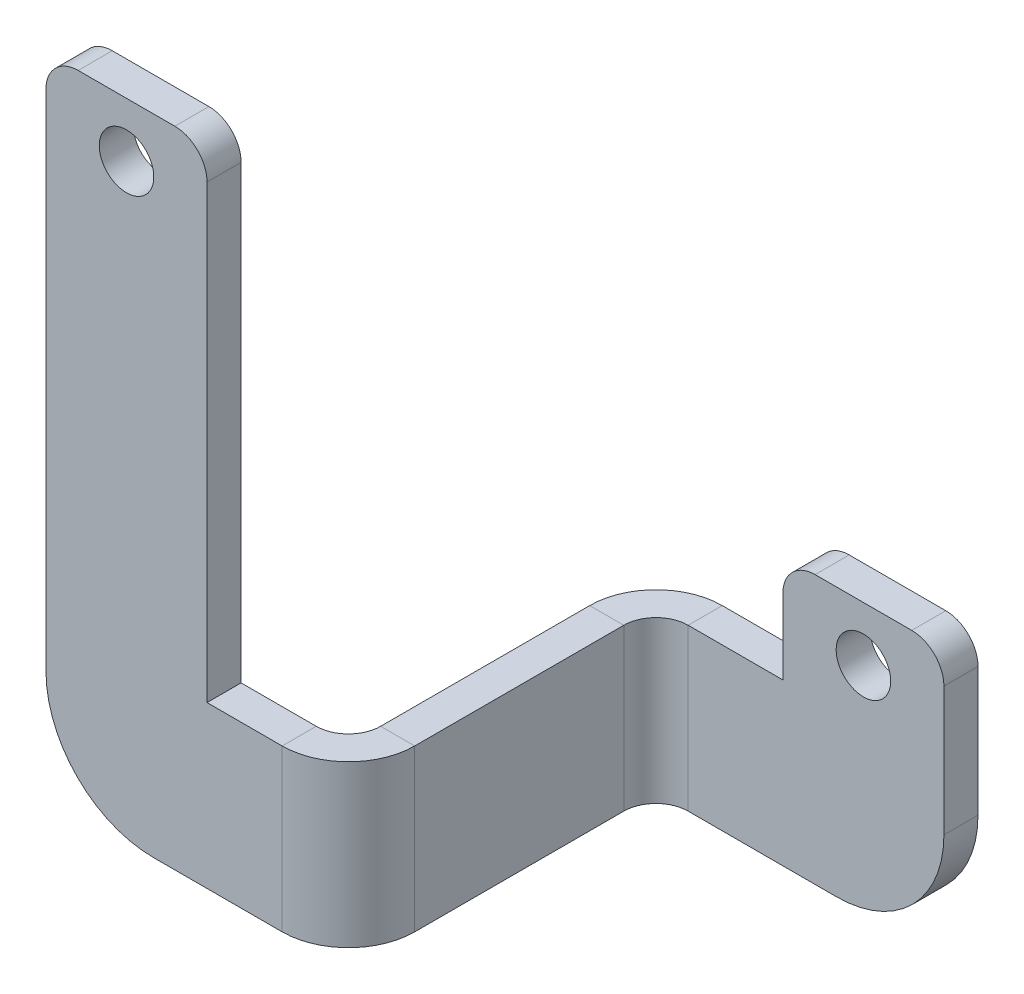
SolidWorks part; units mm, degrees
note: The reader was unsure of these and kept them because the rebuilt part matched: flange length of "Edge-Flange1", "Edge-Flange2".
material "Custom Plastic"
ref_plane "X-Y Datum" through (0, 0, 0) normal (0, 0, 1) x (1, 0, 0)
ref_plane "X-Z Datum" through (0, 0, 0) normal (0, 1, 0) x (1, 0, 0)
ref_plane "Y-Z Datum" through (0, 0, 0) normal (1, 0, 0) x (0, 0, -1)
sketch "Sketch1" plane through (0, 0, 0) normal (0, 0, 1) x (1, 0, 0)
  line L1 (-12.5, -7.5) -> (12.5, -7.5)
  line L2 (-12.5, -7.5) -> (-12.5, 7.5)
  line L3 (-12.5, 7.5) -> (12.5, 7.5)
  line L4 (12.5, -7.5) -> (12.5, 7.5)
  line L5 (-12.5, -7.5) -> (12.5, 7.5) construction
  line L6 (-12.5, 7.5) -> (12.5, -7.5) construction
  point P0 (0, 0)
  dimension "D1" = 25
  dimension "D2" = 15
base flange "Base-Flange1" sketch "Sketch1" thickness 3.175 reverse thickness direction no parameters "D1"=10
edge flange "Edge-Flange1" sketch "Sketch8" flange angle 90 flange length 28.65 flange position material outside bend radius 3 thickness 3.175 parameters "D6"=10
sketch "Sketch8" plane through (12.5, 0, -3.175) normal (-1, 0, 0) x (0, 1, 0)
  line L2 (-7.5, 0) -> (-7.5, 25.475)
  line L3 (-7.5, 25.475) -> (7.5, 25.475)
  line L4 (7.5, 25.475) -> (7.5, 0)
  line L5 (7.5, 0) -> (-7.5, 0) construction
  line L6 (7.5, 0) -> (-7.5, 0)
bend "EdgeBend1" bend radius 3 bend angle 90 parameters "D5"=1
edge flange "Edge-Flange2" sketch "Sketch11" flange angle 90 flange length 30 flange position material outside bend radius 3 thickness 3.175 parameters "D6"=10
sketch "Sketch11" plane through (15.675, 0, -28.65) normal (0, 0, 1) x (0, -1, 0)
  line L2 (-7.5, 0) -> (-7.5, 26.825)
  line L3 (-7.5, 26.825) -> (7.5, 26.825)
  line L4 (7.5, 26.825) -> (7.5, 0)
  line L5 (7.5, 0) -> (-7.5, 0) construction
  line L6 (7.5, 0) -> (-7.5, 0)
bend "EdgeBend2" bend radius 3 bend angle 90 parameters "D5"=2
sketch "Sketch12" plane through (0, 7.5, 0) normal (0, 1, 0) x (1, 0, 0)
  line L0 (9.5, 0) -> (-12.5, 0) construction
  line L1 (-12.5, 3.175) -> (2.5, 3.175)
  line L2 (-12.5, 3.175) -> (-12.5, 0)
  line L3 (-12.5, 0) -> (2.5, 0)
  line L4 (2.5, 3.175) -> (2.5, 0)
  dimension "D1" = 15
extrude "Boss-Extrude1" add sketch "Sketch12" along normal blind 45
sketch "Sketch15" plane through (0, 0, -3.175) normal (0, 0, -1) x (-1, 0, 0)
  line L0 (5, 52.5) -> (5, 47.42)
  line L3 (-2.5, 52.5) -> (12.5, 52.5) construction
  circle A2 centre (5, 47.42) radius 2.54
  dimension "D1" = 5.08
extrude "Cut-Extrude2" cut sketch "Sketch15" against normal through all
sketch "Sketch19" plane through (0, 7.5, 0) normal (0, 1, 0) x (1, 0, 0)
  line L0 (42.5, 28.65) -> (18.675, 28.65) construction
  line L1 (42.5, 31.825) -> (27.5, 31.825)
  line L2 (42.5, 31.825) -> (42.5, 28.65)
  line L3 (42.5, 28.65) -> (27.5, 28.65)
  line L4 (27.5, 31.825) -> (27.5, 28.65)
  dimension "D1" = 15
extrude "Boss-Extrude2" add sketch "Sketch19" along normal blind 10
sketch "Sketch21" plane through (0, 0, -31.825) normal (0, 0, -1) x (-1, 0, 0)
  line L0 (-35, 17.5) -> (-35, 12.42)
  line L2 (-42.5, 17.5) -> (-27.5, 17.5) construction
  circle A1 centre (-35, 12.42) radius 2.54
extrude "Cut-Extrude3" cut sketch "Sketch21" against normal through all
fillet "Fillet2" radius 3 4 edges at (27.5, 17.5, -30.2375) (42.5, 17.5, -30.2375) (2.5, 52.5, -1.5875) (-12.5, 52.5, -1.5875)
fillet "Fillet3" radius 10 2 edges at (42.5, -7.5, -30.2375) (-12.5, -7.5, -1.5875)
sketch "Bend-Lines1" [suppressed] plane through (0, 0, 0) normal (0, 1, 0) x (1, 0, 0)
sketch "Bounding-Box1" [suppressed] plane through (0, 0, 0) normal (0, 1, 0) x (1, 0, 0)
sheet metal parameters "Sheet-Metal1" thickness 3.175 parameters "D1"=10
flat pattern "Flat-Pattern1" [suppressed]
sketch "Bend-Lines2" plane through (0, 0, 0) normal (0, 1, 0) x (1, 0, 0)
sketch3d "Bounding-Box2" [suppressed]
  line L0 (15, -7.5, 0) -> (-15, -7.5, 0) construction
  line L1 (15, 7.5, 0) -> (-15, 7.5, 0) construction
  line L2 (15, -7.5, 0) -> (15, 7.5, 0) construction
  line L3 (-15, -7.5, 0) -> (-15, 7.5, 0) construction
sheet metal parameters "Sheet-Metal2" thickness 3.175 parameters "D1"=10
flat pattern "Flat-Pattern1"
sketch "Bend-Lines2" plane through (0, 0, 0) normal (0, 0, 1) x (1, 0, 0)
  line L0 (15.603, -7.5) -> (15.603, 7.5) construction
  line L1 (15.603, -7.5) -> (15.603, 7.5) construction
sketch3d "Bounding-Box2" [suppressed]
  line L0 (-15, -7.5, 0) -> (38.031, -7.5, 0) construction
  line L1 (-15, 7.5, 0) -> (38.031, 7.5, 0) construction
  line L2 (-15, -7.5, 0) -> (-15, 7.5, 0) construction
  line L3 (38.031, -7.5, 0) -> (38.031, 7.5, 0) construction
bend of the flat pattern "Flatten-<EdgeBend1>1"
sheet metal parameters "Sheet-Metal3" thickness 3.175 parameters "D1"=10
flat pattern "Flat-Pattern1"
sketch "Bend-Lines2" plane through (0, 0, 0) normal (0, 0, 1) x (1, 0, 0)
  line L0 (23.103, -7.5) -> (23.103, 7.5) construction
  line L1 (23.103, -7.5) -> (23.103, 7.5) construction
  line L2 (46.134, -7.5) -> (46.134, 7.5) construction
  line L3 (46.134, -7.5) -> (46.134, 7.5) construction
sketch3d "Bounding-Box2" [suppressed]
  line L0 (-22.5, -7.5, 0) -> (73.5621, -7.5, 0) construction
  line L1 (-22.5, 7.5, 0) -> (73.5621, 7.5, 0) construction
  line L2 (-22.5, -7.5, 0) -> (-22.5, 7.5, 0) construction
  line L3 (73.5621, -7.5, 0) -> (73.5621, 7.5, 0) construction
bend of the flat pattern "Flatten-<EdgeBend1>1"
bend of the flat pattern "Flatten-<EdgeBend2>1"
sheet metal parameters "Sheet-Metal4" thickness 3.175 parameters "D1"=10
flat pattern "Flat-Pattern1"
sketch "Bend-Lines2" plane through (0, 0, 0) normal (0, 0, 1) x (1, 0, 0)
  line L0 (20.603, -7.5) -> (20.603, 7.5) construction
  line L1 (20.603, -7.5) -> (20.603, 7.5) construction
  line L2 (53.634, -7.5) -> (53.634, 7.5) construction
  line L3 (53.634, -7.5) -> (53.634, 7.5) construction
sketch3d "Bounding-Box2" [suppressed]
  line L0 (-20, -7.5, 0) -> (81.0621, -7.5, 0) construction
  line L1 (-20, 41.5, 0) -> (81.0621, 41.5, 0) construction
  line L2 (-20, -7.5, 0) -> (-20, 41.5, 0) construction
  line L3 (81.0621, -7.5, 0) -> (81.0621, 41.5, 0) construction
bend of the flat pattern "Flatten-<EdgeBend1>1"
bend of the flat pattern "Flatten-<EdgeBend2>1"
sheet metal parameters "Sheet-Metal6" thickness 3.175 parameters "D1"=10
flat pattern "Flat-Pattern1" [suppressed]
sketch "Bend-Lines2" plane through (0, 0, 0) normal (0, 0, 1) x (1, 0, 0)
  line L0 (25.603, -10) -> (25.603, 10) construction
  line L1 (25.603, -10) -> (25.603, 10) construction
  line L2 (51.634, -10) -> (51.634, 10) construction
  line L3 (51.634, -10) -> (51.634, 10) construction
sketch3d "Bounding-Box2" [suppressed]
  line L0 (-25, -10, 0) -> (74.0621, -10, 0) construction
  line L1 (-25, 32, 0) -> (74.0621, 32, 0) construction
  line L2 (-25, -10, 0) -> (-25, 32, 0) construction
  line L3 (74.0621, -10, 0) -> (74.0621, 32, 0) construction
bend of the flat pattern "Flatten-<EdgeBend1>1"
bend of the flat pattern "Flatten-<EdgeBend2>1"
sketch "Sketch14-1" [suppressed] plane through (24.0621, 0, -3.175) normal (0, 0, -1) x (-1, 0, 0)
  line L0 (-50, 0) -> (-44.92, 0)
  circle A0 centre (-44.92, 0) radius 2.54
  dimension "D1" = 5.08
sheet metal parameters "Sheet-Metal7" thickness 3.175 parameters "D1"=10
flat pattern "Flat-Pattern1"
sketch "Bend-Lines2" plane through (0, 0, 0) normal (0, 0, 1) x (1, 0, 0)
  line L0 (23.103, -7.5) -> (23.103, 7.5) construction
  line L1 (23.103, -7.5) -> (23.103, 7.5) construction
  line L2 (49.134, -7.5) -> (49.134, 7.5) construction
  line L3 (49.134, -7.5) -> (49.134, 7.5) construction
sketch3d "Bounding-Box2" [suppressed]
  line L0 (-22.5, -7.5, 0) -> (76.5621, -7.5, 0) construction
  line L1 (-22.5, 31.5, 0) -> (76.5621, 31.5, 0) construction
  line L2 (-22.5, -7.5, 0) -> (-22.5, 31.5, 0) construction
  line L3 (76.5621, -7.5, 0) -> (76.5621, 31.5, 0) construction
bend of the flat pattern "Flatten-<EdgeBend1>1"
bend of the flat pattern "Flatten-<EdgeBend2>1"
sheet metal parameters "Sheet-Metal8" thickness 3.175 parameters "D1"=10
flat pattern "Flat-Pattern1"
sketch "Bend-Lines2" plane through (0, 0, 0) normal (0, 0, 1) x (1, 0, 0)
  line L0 (13.103, -7.5) -> (13.103, 7.5) construction
  line L1 (13.103, -7.5) -> (13.103, 7.5) construction
  line L2 (39.784, -7.5) -> (39.784, 7.5) construction
  line L3 (39.784, -7.5) -> (39.784, 7.5) construction
sketch3d "Bounding-Box2" [suppressed]
  line L0 (-12.5, -7.5, 0) -> (67.2121, -7.5, 0) construction
  line L1 (-12.5, 52.5, 0) -> (67.2121, 52.5, 0) construction
  line L2 (-12.5, -7.5, 0) -> (-12.5, 52.5, 0) construction
  line L3 (67.2121, -7.5, 0) -> (67.2121, 52.5, 0) construction
bend of the flat pattern "Flatten-<EdgeBend1>1"
bend of the flat pattern "Flatten-<EdgeBend2>1"
